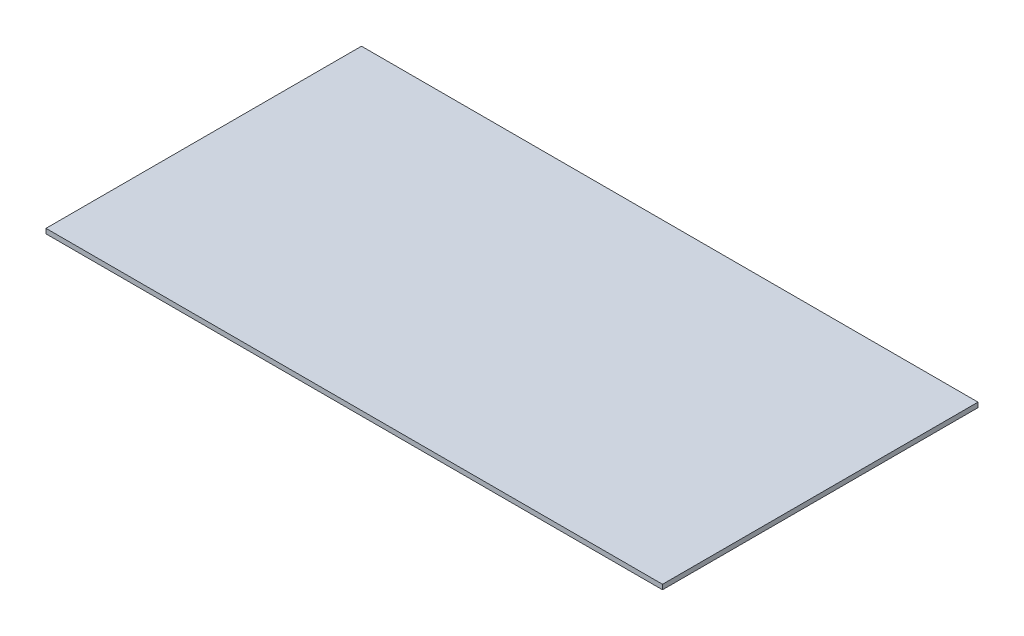
SolidWorks part; units mm, degrees
ref_plane "Front Plane" through (0, 0, 0) normal (0, 0, 1) x (1, 0, 0)
ref_plane "Top Plane" through (0, 0, 0) normal (0, 1, 0) x (1, 0, 0)
ref_plane "Right Plane" through (0, 0, 0) normal (1, 0, 0) x (0, 0, -1)
sketch "Sketch1" plane through (0, 0, 0) normal (0, 1, 0) x (1, 0, 0)
  line L0 (812.8, 0) -> (812.8, 419.1) construction
  line L5 (785.749, 415.925) -> (519.049, 415.925) construction
  line L7 (0, 0) -> (812.8, 0)
  line L8 (0, 0) -> (0, 415.925)
  line L9 (0, 415.925) -> (812.8, 415.925)
  line L10 (812.8, 0) -> (812.8, 415.925)
extrude "Boss-Extrude1" add sketch "Sketch1" along normal blind 6.35
